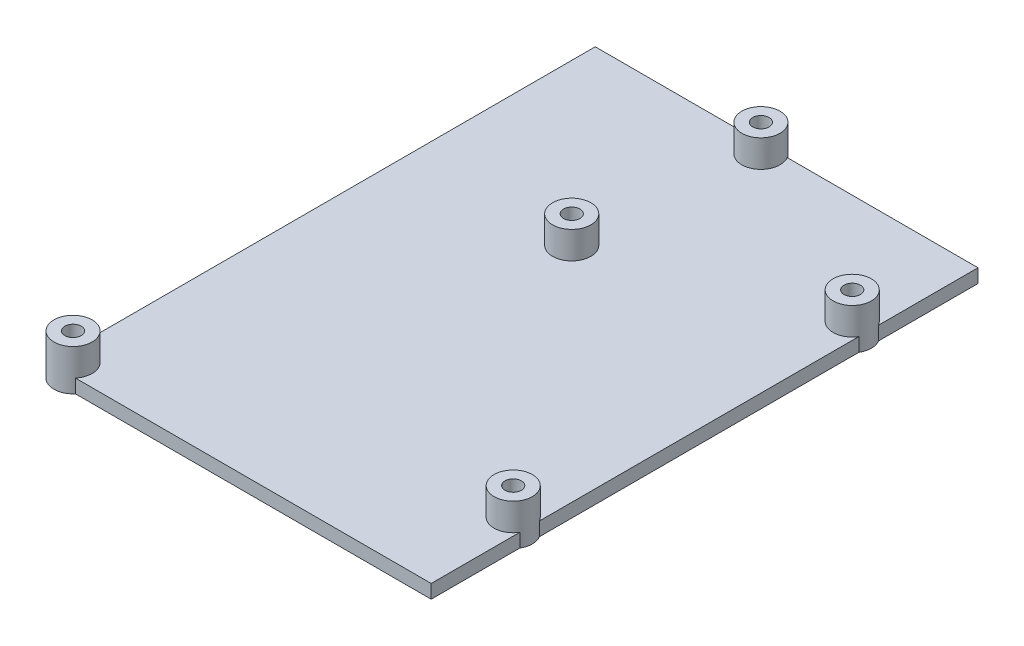
SolidWorks part; units mm, degrees
material "6061-T6 (SS)"
ref_plane "Front Plane" through (0, 0, 0) normal (0, 0, 1) x (1, 0, 0)
ref_plane "Top Plane" through (0, 0, 0) normal (0, 1, 0) x (1, 0, 0)
ref_plane "Right Plane" through (0, 0, 0) normal (1, 0, 0) x (0, 0, -1)
ref_axis "Axis1" through (0, 0, 55) along (0, 0, -1)
sketch "Sketch1" plane through (0, 0, 0) normal (0, 1, 0) x (1, 0, 0)
  line L0 (-125, 0) -> (0, 0) construction
  line L1 (125, 0) -> (125, 125) construction
  line L2 (125, 125) -> (-125, 125) construction
  line L3 (-125, 125) -> (-125, 0) construction
  line L4 (41.25, 3.75) -> (41.25, 1.5) construction
  line L5 (39, 101.5) -> (109, 101.5)
  line L6 (39, 101.5) -> (39, 1.5)
  line L7 (39, 1.5) -> (109, 1.5)
  line L8 (109, 101.5) -> (109, 1.5)
  line L9 (39, 101.5) -> (109, 1.5) construction
  line L10 (39, 1.5) -> (109, 101.5) construction
  line L11 (41.25, 3.75) -> (39, 3.75) construction
  line L12 (-114.29, 77.51) -> (-116.54, 77.51) construction
  line L13 (78.2, 11.5) -> (87.2, 11.5)
  line L14 (78.2, 11.5) -> (78.2, 1.5)
  line L15 (78.2, 1.5) -> (87.2, 1.5)
  line L16 (87.2, 11.5) -> (87.2, 1.5)
  line L17 (78.2, 11.5) -> (87.2, 1.5) construction
  line L18 (78.2, 1.5) -> (87.2, 11.5) construction
  line L19 (90.5, 16.5) -> (106.5, 16.5)
  line L20 (90.5, 16.5) -> (90.5, 1.5)
  line L21 (90.5, 1.5) -> (106.5, 1.5)
  line L22 (106.5, 16.5) -> (106.5, 1.5)
  line L23 (90.5, 16.5) -> (106.5, 1.5) construction
  line L24 (90.5, 1.5) -> (106.5, 16.5) construction
  line L25 (-116.54, 113.59) -> (-93.46, 113.59)
  line L26 (-116.54, 113.59) -> (-116.54, 71.41)
  line L27 (-116.54, 71.41) -> (-93.46, 71.41)
  line L28 (-93.46, 113.59) -> (-93.46, 71.41)
  line L29 (-116.54, 113.59) -> (-93.46, 71.41) construction
  line L30 (-116.54, 71.41) -> (-93.46, 113.59) construction
  line L31 (-114.29, 77.51) -> (-114.29, 71.41) construction
  line L32 (-95.71, 107.49) -> (-95.71, 113.59) construction
  line L33 (-95.71, 107.49) -> (-93.46, 107.49) construction
  line L34 (-64.5, 85.45) -> (-68, 85.45) construction
  line L35 (-65, 88.95) -> (-15, 88.95)
  line L36 (-68, 85.95) -> (-68, 6.95)
  line L37 (-65, 3.95) -> (-15, 3.95)
  line L38 (-12, 85.95) -> (-12, 6.95)
  line L39 (-68, 88.95) -> (-12, 3.95) construction
  line L40 (-68, 3.95) -> (-12, 88.95) construction
  line L41 (-64.5, 85.45) -> (-15.5, 85.45) construction
  line L42 (-64.5, 85.45) -> (-64.5, 27.45) construction
  line L43 (-64.5, 27.45) -> (-15.5, 27.45) construction
  line L44 (-15.5, 85.45) -> (-15.5, 27.45) construction
  line L45 (0, 0) -> (0, 125) construction
  line L46 (0, 0) -> (125, 0) construction
  line L47 (-64.5, 85.45) -> (-64.5, 88.95) construction
  line L48 (74, 0) -> (74, 125) construction
  line L49 (-65.69, 22.9) -> (-49.81, 22.9)
  line L50 (-65.69, 22.9) -> (-65.69, 1.5)
  line L51 (-65.69, 1.5) -> (-49.81, 1.5)
  line L52 (-49.81, 22.9) -> (-49.81, 1.5)
  line L53 (-65.69, 22.9) -> (-49.81, 1.5) construction
  line L54 (-65.69, 1.5) -> (-49.81, 22.9) construction
  line L55 (-45.65, 19.42) -> (-32.35, 19.42)
  line L56 (-45.65, 19.42) -> (-45.65, 1.5)
  line L57 (-45.65, 1.5) -> (-32.35, 1.5)
  line L58 (-32.35, 19.42) -> (-32.35, 1.5)
  line L59 (-45.65, 19.42) -> (-32.35, 1.5) construction
  line L60 (-45.65, 1.5) -> (-32.35, 19.42) construction
  line L61 (-27.65, 19.42) -> (-14.35, 19.42)
  line L62 (-27.65, 19.42) -> (-27.65, 1.5)
  line L63 (-27.65, 1.5) -> (-14.35, 1.5)
  line L64 (-14.35, 19.42) -> (-14.35, 1.5)
  line L65 (-27.65, 19.42) -> (-14.35, 1.5) construction
  line L66 (-27.65, 1.5) -> (-14.35, 19.42) construction
  line L67 (-40, 0) -> (-40, 125) construction
  line L68 (-114.29, 11.41) -> (-114.29, 17.51) construction
  line L69 (-116.54, 53.59) -> (-93.46, 53.59)
  line L70 (-116.54, 53.59) -> (-116.54, 11.41)
  line L71 (-116.54, 11.41) -> (-93.46, 11.41)
  line L72 (-93.46, 53.59) -> (-93.46, 11.41)
  line L73 (-116.54, 53.59) -> (-93.46, 11.41) construction
  line L74 (-116.54, 11.41) -> (-93.46, 53.59) construction
  line L75 (-114.29, 17.51) -> (-116.54, 17.51) construction
  line L76 (-95.71, 53.59) -> (-95.71, 47.49) construction
  line L77 (-95.71, 47.49) -> (-93.46, 47.49) construction
  line L78 (-105, 0) -> (-105, 32.5) construction
  line L79 (-105, 32.5) -> (-105, 92.5) construction
  line L80 (-105, 92.5) -> (-105, 125) construction
  line L81 (-64.5, 27.45) -> (-15.5, 85.45) construction
  line L82 (-15.5, 27.45) -> (-64.5, 85.45) construction
  circle A0 centre (106, 81.5) radius 1.75
  circle A1 centre (106, 19.5) radius 1.75
  circle A2 centre (71.1, 99.7) radius 1.75
  circle A3 centre (68.3, 67.9) radius 1.75
  circle A4 centre (41.25, 3.75) radius 1.75
  circle A5 centre (-95.71, 107.49) radius 1.4
  circle A6 centre (-114.29, 77.51) radius 1.4
  arc A7 (-15, 3.95) -> (-12, 6.95) centre (-15, 6.95) ccw
  arc A8 (-68, 6.95) -> (-65, 3.95) centre (-65, 6.95) ccw
  arc A9 (-15, 88.95) -> (-12, 85.95) centre (-15, 85.95) cw
  arc A10 (-65, 88.95) -> (-68, 85.95) centre (-65, 85.95) ccw
  circle A11 centre (-64.5, 85.45) radius 1.375
  circle A12 centre (-15.5, 85.45) radius 1.375
  circle A13 centre (-64.5, 27.45) radius 1.375
  circle A14 centre (-15.5, 27.45) radius 1.375
  circle A15 centre (-95.71, 47.49) radius 1.4
  circle A16 centre (-114.29, 17.51) radius 1.4
  circle A17 centre (41.25, 3.75) radius 2.84
  point P0 (74, 51.5)
  point P3 (-105, 92.5)
  point P4 (0, 0)
  point P24 (82.7, 6.5)
  point P30 (98.5, 9)
  point P47 (-40, 46.45)
  point P65 (-39, 10.46)
  point P69 (-57.75, 12.2)
  point P84 (-21, 10.46)
  point P89 (-105, 32.5)
  point P111 (-40, 56.45)
  dimension "D5" = 3.5
  dimension "D26" = 3
  dimension "D27" = 2.75
  dimension "D44" = 2.8
  dimension "D49" = 5.68
  dimension "D1" = 250
  dimension "D2" = 125
  dimension "D3" = 100
  dimension "D4" = 70
  dimension "D6" = 20
  dimension "D7" = 3
  dimension "D8" = 82
  dimension "D9" = 1.8
  dimension "D10" = 37.9
  dimension "D11" = 33.6
  dimension "D12" = 40.7
  dimension "D13" = 2.25
  dimension "D14" = 9
  dimension "D15" = 10
  dimension "D16" = 26.3
  dimension "D17" = 16
  dimension "D18" = 15
  dimension "D19" = 10.5
  dimension "D20" = 23.08
  dimension "D21" = 42.18
  dimension "D22" = 6.1
  dimension "D23" = 2.25
  dimension "D24" = 85
  dimension "D25" = 56
  dimension "D28" = 58
  dimension "D29" = 49
  dimension "D30" = 10.25
  dimension "D31" = 29
  dimension "D32" = 47
  dimension "D33" = 21.4
  dimension "D34" = 15.88
  dimension "D35" = 2.45
  dimension "D36" = 13.3
  dimension "D37" = 17.92
  dimension "D38" = 2.45
  dimension "D39" = 2.45
  dimension "D40" = 2.25
  dimension "D41" = 1.5
  dimension "D42" = 40
  dimension "D43" = 1.5
  dimension "D45" = 60
  dimension "D46" = 3.5
  dimension "D47" = 20
  dimension "D48" = 16
sketch "Sketch2" plane through (0, 0, 0) normal (0, 1, 0) x (1, 0, 0)
  line L0 (39, 101.5) -> (109, 1.5) construction
  line L1 (39, 101.5) -> (109, 101.5)
  line L2 (39, 101.5) -> (39, 1.5)
  line L3 (39, 1.5) -> (109, 1.5)
  line L4 (109, 101.5) -> (109, 1.5)
  line L5 (39, 101.5) -> (109, 1.5) construction
  line L6 (39, 1.5) -> (109, 101.5) construction
  circle A0 centre (41.25, 3.75) radius 1.5 construction
  circle A1 centre (106, 19.5) radius 1.5 construction
  circle A2 centre (68.3, 67.9) radius 1.5 construction
  circle A3 centre (106, 81.5) radius 1.5 construction
  circle A4 centre (71.1, 99.7) radius 1.5 construction
  circle A5 centre (71.1, 99.7) radius 3.5 construction
  circle A6 centre (106, 81.5) radius 3.5 construction
  circle A7 centre (68.3, 67.9) radius 3.5 construction
  circle A8 centre (41.25, 3.75) radius 3.5 construction
  circle A9 centre (106, 19.5) radius 3.5 construction
  point P0 (74, 51.5)
  dimension "D1" = 3
  dimension "D2" = 2
extrude "Boss-Extrude1" add sketch "Sketch2" along normal blind 2.5
sketch "Sketch3" plane through (0, 2.5, 0) normal (0, 1, 0) x (1, 0, 0)
  circle A0 centre (41.25, 3.75) radius 3.5 construction
  circle A1 centre (41.25, 3.75) radius 1.5 construction
  circle A2 centre (106, 19.5) radius 3.5 construction
  circle A3 centre (106, 19.5) radius 1.5 construction
  circle A4 centre (106, 81.5) radius 1.5 construction
  circle A5 centre (106, 81.5) radius 3.5 construction
  circle A6 centre (68.3, 67.9) radius 3.5 construction
  circle A7 centre (68.3, 67.9) radius 1.5 construction
  circle A8 centre (71.1, 99.7) radius 3.5 construction
  circle A9 centre (71.1, 99.7) radius 1.5 construction
  circle A10 centre (41.25, 3.75) radius 3.5
  circle A11 centre (41.25, 3.75) radius 1.5
  circle A12 centre (106, 19.5) radius 3.5
  circle A13 centre (106, 19.5) radius 1.5
  circle A14 centre (106, 81.5) radius 1.5
  circle A15 centre (106, 81.5) radius 3.5
  circle A16 centre (68.3, 67.9) radius 3.5
  circle A17 centre (68.3, 67.9) radius 1.5
  circle A18 centre (71.1, 99.7) radius 3.5
  circle A19 centre (71.1, 99.7) radius 1.5
extrude "Boss-Extrude2" add sketch "Sketch3" along normal blind 5 and the other way up to surface (2.5 mm away) other way up to face at (74, 0, -51.5)
equation "\"D16@Sketch1\"=22.8+3.5"
equation "\"D19@Sketch1\"=7+3.5"
